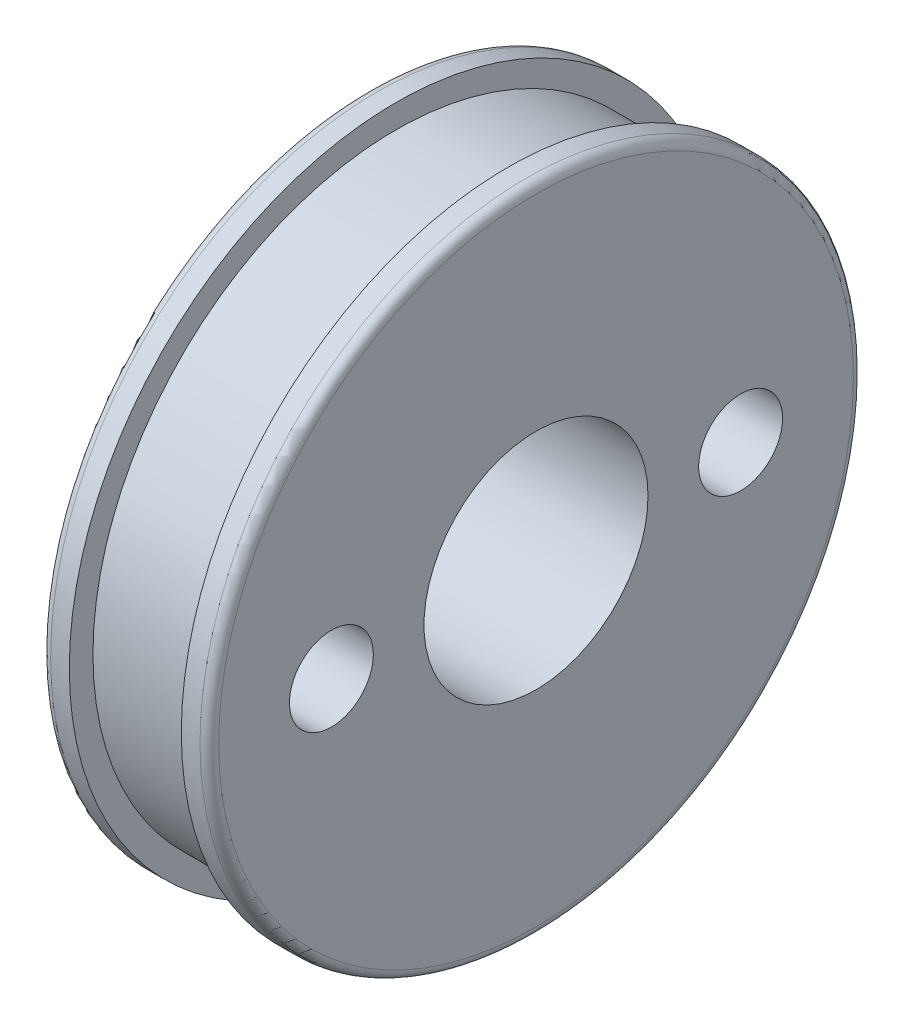
SolidWorks part; units mm, degrees
material "ABS"
ref_plane "Front Plane" through (0, 0, 0) normal (1, 0, 0) x (0, 1, 0)
ref_plane "Top Plane" through (0, 0, 0) normal (0, 0, 1) x (0, 1, 0)
ref_plane "Right Plane" through (0, 0, 0) normal (0, 1, 0) x (-1, 0, 0)
sketch "Sketch1" plane through (0, 0, 0) normal (1, 0, 0) x (0, 1, 0)
  circle A0 centre (0, 0) radius 16.2338
  circle A1 centre (0, 0) radius 14.825 construction
  circle A2 centre (0, 0) radius 14.0852 construction
  circle A3 centre (0, 0) radius 15.2789 construction
  dimension "D1" = 32.4676
  dimension "D2" = 29.6501
  dimension "D3" = 28.1704
  dimension "D4" = 30.5577
extrude "Boss-Extrude1" add sketch "Sketch1" along normal mid plane 6
sketch "Sketch3" plane through (3, 0, 0) normal (1, 0, 0) x (0, 1, 0)
  line L0 (0, 0) -> (14.825, 0) construction
  line L1 (0, 0) -> (15.2787, 0.0761) construction
  line L2 (0, 0) -> (15.264, -0.6737) construction
  line L3 (15.264, -0.6737) -> (14.8106, -0.6537)
  line L4 (15.264, -0.6737) -> (20.4848, -0.9041)
  line L5 (20.4848, 4.4648) -> (20.4848, -0.9041)
  line L6 (14.825, 0) -> (14.0852, 0)
  line L7 (14.8106, -0.6537) -> (14.0715, -0.621)
  circle A0 centre (0, 0) radius 15.2789 construction
  circle A1 centre (0, 0) radius 14.825 construction
  circle A2 centre (0, 0) radius 14.0852 construction
  arc A3 (14.0852, 0) -> (14.0715, -0.621) centre (0, 0) cw
  spline S0 degree 4 poles (14.825, 0) (14.836, 0.0002) (14.8667, 0.0016) (14.9246, 0.007) (15.0188, 0.0199) (15.138, 0.0421) (15.291, 0.0776) (15.4696, 0.1279) (15.6636, 0.192) (15.872, 0.2713) (16.0774, 0.3587) (16.2795, 0.4535) (16.4783, 0.5547) (16.7158, 0.6852) (16.9958, 0.8526) (17.3155, 1.0639) (17.6686, 1.3216) (18.0175, 1.6029) (18.3514, 1.8949) (18.6772, 2.2068) (18.9842, 2.5203) (19.2902, 2.8623) (19.5662, 3.1863) (19.8604, 3.5665) (20.0935, 3.8783) (20.3842, 4.307) (20.5508, 4.5654) (20.7399, 4.8734) (20.8206, 5.0132) (20.8705, 5.0992) knots 0 0 0 0 0 0.005377 0.015084 0.028532 0.04661 0.064855 0.092111 0.119476 0.146842 0.174209 0.201575 0.228941 0.256307 0.307035 0.361767 0.4165 0.471232 0.525964 0.580697 0.635429 0.690161 0.744894 0.799626 0.854358 0.909091 0.954545 1 1 1 1 1 construction
  spline S1 degree 4 poles (14.825, 0) (14.836, 0.0002) (14.8667, 0.0016) (14.9246, 0.007) (15.0188, 0.0199) (15.138, 0.0421) (15.291, 0.0776) (15.4696, 0.1279) (15.6636, 0.192) (15.872, 0.2713) (16.0774, 0.3587) (16.2795, 0.4535) (16.4783, 0.5547) (16.7158, 0.6852) (16.9958, 0.8526) (17.3155, 1.0639) (17.6686, 1.3216) (18.0175, 1.6029) (18.3514, 1.8949) (18.6772, 2.2068) (18.9842, 2.5203) (19.2902, 2.8623) (19.5662, 3.1863) (19.8604, 3.5665) (20.0935, 3.8783) (20.3212, 4.2141) (20.43, 4.3795) (20.4848, 4.4648) knots 0 0 0 0 0 0.005377 0.015084 0.028532 0.04661 0.064855 0.092111 0.119476 0.146842 0.174209 0.201575 0.228941 0.256307 0.307035 0.361767 0.4165 0.471232 0.525964 0.580697 0.635429 0.690161 0.744894 0.799626 0.854358 0.909091 0.909091 0.909091 0.909091 0.909091
  circle M1 centre (0, 0) radius 16.2338
  dimension "D1" = 2.813
extrude "Cut-Extrude1" [suppressed] cut sketch "Sketch3" against normal through all contours S1 L6 A3 L3 L4 M1
mirror "Mirror1" [suppressed]
pattern_circular "CirPattern6" [suppressed] count 32 over 360 of bodies 103
sketch "Sketch4" plane through (3, 0, 0) normal (1, 0, 0) x (0, 1, 0)
  circle A0 centre (0, 0) radius 17.5
  dimension "D1" = 35
extrude "Boss-Extrude2" add sketch "Sketch4" along normal blind 1.5
fillet "Fillet1" radius 0.5 1 edges at (4.5, 0, -17.5)
mirror "Mirror2" about plane through (0, 0, 0) normal (1, 0, 0) of "Boss-Extrude2", "Fillet1"
sketch "Sketch6" plane through (0, 0, 0) normal (1, 0, 0) x (0, 1, 0)
  line L0 (0, 10.9601) -> (0, -10.9601) construction
  circle A0 centre (0, 0) radius 6
  point P12 (0, 0)
  dimension "D1" = 12
  dimension "D2" = 21.9202
extrude "Cut-Extrude2" cut sketch "Sketch6" against normal through all both and the other way through all
hole_wizard "#8 Clearance Hole1" positions "Sketch9" profile "Sketch10" hole size "#8" standard "ANSI Inch" end condition up to next
sketch "Sketch9" plane through (4.5, 0, 0) normal (1, 0, 0) x (0, 0, -1)
  point P0 (10.9601, 0)
  point P3 (-10.9601, 0)
sketch "Sketch10" plane through (4.5, 0, -10.9601) normal (0, 1, 0) x (0, 0, -1)
  line L0 (0, 0) -> (0, 9)
  line L1 (0, 9) -> (2.2479, 9)
  line L2 (2.2479, 9) -> (2.2479, 0)
  line L5 (2.2479, 0) -> (0, 0)
  line L11 (0, -6.35) -> (0, 107.95) construction
  dimension "Thru Hole Dia." = 4.4958
  dimension "Thru Hole Depth" = 9
equation "\"DiametralPitch\"= pi / \"Pitch\""
equation "\"NumberTeeth\"= 32"
equation "\"PressureAngle\"= 14"
equation "\"PitchDiameter\"= \"NumberTeeth\" / \"DiametralPitch\""
equation "\"BaseDiameter\"= \"PitchDiameter\" * cos ( \"PressureAngle\" )"
equation "\"Addendum\"= 1 / \"DiametralPitch\""
equation "\"Dedendum\"= 1.25 / \"DiametralPitch\""
equation "\"AddendumDiameter\"= \"PitchDiameter\" + \"Addendum\" + \"Addendum\""
equation "\"DedendumDiameter\"= \"PitchDiameter\" - \"Dedendum\" - \"Dedendum\""
equation "\"ToothSpacing\"= 360 / ( 4 * \"NumberTeeth\" )"
equation "\"D1@Sketch1\"=\"AddendumDiameter\""
equation "\"D2@Sketch1\"=\"BaseDiameter\""
equation "\"D3@Sketch1\"=\"DedendumDiameter\""
equation "\"D4@Sketch1\"=\"PitchDiameter\""
equation "\"D1@Sketch3\"=\"ToothSpacing\""
equation "\"D1@CirPattern6\"=\"NumberTeeth\""
equation "\"D2@Sketch6\"=0.863in"
equation "\"Pitch\"= 3"
